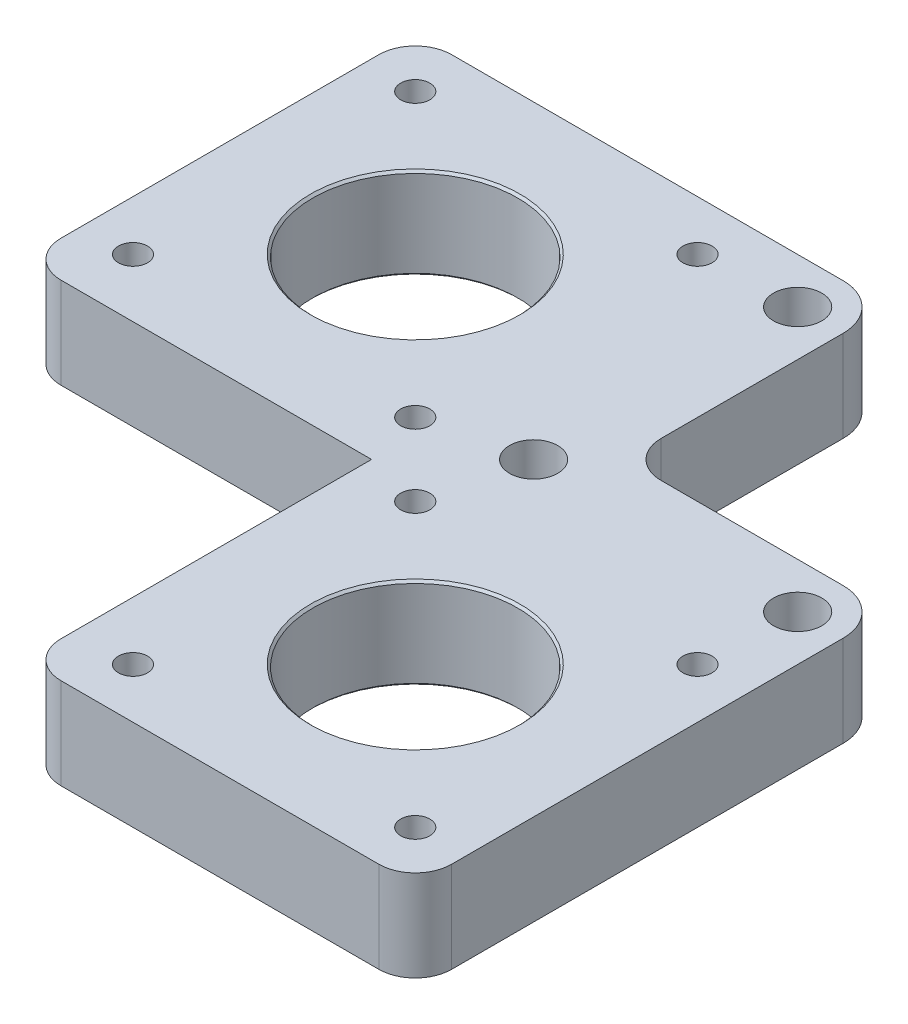
SolidWorks part; units mm, degrees
material "AISI 1045 Steel, cold drawn"
ref_plane "Front Plane" through (0, 0, 0) normal (0, 0, 1) x (1, 0, 0)
ref_plane "Top Plane" through (0, 0, 0) normal (0, 1, 0) x (1, 0, 0)
ref_plane "Right Plane" through (0, 0, 0) normal (1, 0, 0) x (0, 0, -1)
sketch "Sketch1" plane through (0, 0, 0) normal (0, 1, 0) x (1, 0, 0)
  line L1 (60, -21) -> (18, -21) construction
  line L2 (60, -21) -> (60, 21) construction
  line L3 (60, 21) -> (18, 21) construction
  line L4 (18, -21) -> (18, 21) construction
  line L5 (60, -21) -> (18, 21) construction
  line L6 (60, 21) -> (18, -21) construction
  line L7 (21, 18) -> (-21, 18) construction
  line L8 (21, 18) -> (21, 60) construction
  line L9 (21, 60) -> (-21, 60) construction
  line L10 (-21, 18) -> (-21, 60) construction
  line L11 (21, 18) -> (-21, 60) construction
  line L12 (21, 60) -> (-21, 18) construction
  line L14 (60, -21) -> (60, 31)
  line L15 (60, 31) -> (31, 31)
  line L16 (31, 31) -> (31, 60)
  line L17 (31, 60) -> (-21, 60)
  line L18 (-21, 60) -> (-21, 18)
  line L19 (-21, 18) -> (18, 18)
  line L20 (18, 18) -> (18, -21)
  line L21 (18, -21) -> (60, -21)
  point P0 (39, 0)
  point P5 (0, 39)
  dimension "D1" = 42
  dimension "D2" = 39
  dimension "D3" = 39
  dimension "D4" = 10
  dimension "D5" = 10
extrude "Boss-Extrude1" add sketch "Sketch1" along normal blind 10
hole_wizard "Ø22.5 (22.5) Diameter Hole1" positions "Sketch5" profile "Sketch7" hole size "Ø22.5" standard "ANSI Metric" end condition through all
sketch "Sketch5" plane through (0, 10, 0) normal (0, 1, 0) x (1, 0, 0)
  point P0 (0, 39)
  point P3 (39, 0)
sketch "Sketch7" plane through (0, 10, -39) normal (1, 0, 0) x (0, 0, 1)
  line L0 (0, 0) -> (0, 10)
  line L1 (0, 10) -> (11.25, 10)
  line L2 (11.25, 10) -> (11.25, 0)
  line L5 (11.25, 0) -> (0, 0)
  line L11 (0, -6.35) -> (0, 107.95) construction
  dimension "Thru Hole Dia." = 22.5
  dimension "Thru Hole Depth" = 10
sketch "Sketch8" plane through (0, 0, 0) normal (0, 1, 0) x (1, 0, 0)
  line L0 (21, 60) -> (-21, 18) construction
  line L1 (15.5, 23.5) -> (-15.5, 23.5)
  line L2 (15.5, 23.5) -> (15.5, 54.5)
  line L3 (15.5, 54.5) -> (-15.5, 54.5)
  line L4 (-15.5, 23.5) -> (-15.5, 54.5)
  line L5 (15.5, 23.5) -> (-15.5, 54.5) construction
  line L6 (15.5, 54.5) -> (-15.5, 23.5) construction
  line L7 (21, 18) -> (-21, 60) construction
  line L8 (60, 21) -> (18, -21) construction
  line L9 (23.5, -15.5) -> (54.5, -15.5)
  line L10 (23.5, -15.5) -> (23.5, 15.5)
  line L11 (23.5, 15.5) -> (54.5, 15.5)
  line L12 (54.5, -15.5) -> (54.5, 15.5)
  line L13 (23.5, -15.5) -> (54.5, 15.5) construction
  line L14 (23.5, 15.5) -> (54.5, -15.5) construction
  point P0 (0, 39)
  point P9 (39, 0)
  point P17 (39.0542, 0)
  point P19 (0, 0)
  dimension "D1" = 31
hole_wizard "CBORE for M3 SHCS1" positions "Sketch9" profile "Sketch10" counterbore size "M3" standard "ANSI Metric" end condition through all
sketch "Sketch9" plane through (0, 0, 0) normal (0, -1, 0) x (-1, 0, 0)
  point P0 (-54.5, 15.5)
  point P3 (-23.5, 15.5)
  point P6 (-23.5, -15.5)
  point P9 (-54.5, -15.5)
  point P12 (-15.5, 54.5)
  point P15 (-15.5, 23.5)
  point P18 (15.5, 23.5)
  point P21 (15.5, 54.5)
sketch "Sketch10" plane through (54.5, 0, -15.5) normal (1, 0, 0) x (0, 0, -1)
  line L0 (0, 0) -> (0, 10)
  line L1 (0, 10) -> (1.6, 10)
  line L3 (1.6, 10) -> (1.6, 3)
  line L4 (1.6, 3) -> (3.25, 3)
  line L5 (3.25, 3) -> (3.25, 0)
  line L7 (3.25, 0) -> (0, 0)
  line L11 (0, -6.35) -> (0, 107.95) construction
  dimension "Thru Hole Dia." = 3.2
  dimension "Thru Hole Depth" = 10
  dimension "C'Bore Dia." = 6.5
  dimension "C'Bore Depth" = 3
hole_wizard "M5 Clearance Hole1" positions "Sketch11" profile "Sketch12" hole size "M5" standard "ANSI Metric" end condition through all
sketch "Sketch11" plane through (0, 10, 0) normal (0, 1, 0) x (1, 0, 0)
  line L0 (55, 26) -> (26, 26) construction
  line L1 (26, 26) -> (26, 55) construction
  line L3 (31, 31) -> (31, 60) construction
  line L4 (31, 60) -> (-21, 60) construction
  line L5 (60, -21) -> (60, 31) construction
  line L6 (60, 31) -> (31, 31) construction
  point P0 (26, 55)
  point P2 (26, 26)
  point P4 (55, 26)
  dimension "D1" = 5
  dimension "D2" = 5
  dimension "D3" = 5
  dimension "D4" = 5
sketch "Sketch12" plane through (26, 10, -55) normal (1, 0, 0) x (0, 0, 1)
  line L0 (0, 0) -> (0, 10)
  line L1 (0, 10) -> (2.65, 10)
  line L2 (2.65, 10) -> (2.65, 0)
  line L5 (2.65, 0) -> (0, 0)
  line L11 (0, -6.35) -> (0, 107.95) construction
  dimension "Thru Hole Dia." = 5.3
  dimension "Thru Hole Depth" = 10
hole_wizard "Tap Drill for M5x0.8 Tap1" positions "Sketch13" profile "Sketch15" hole size "M5x0.8" standard "ANSI Metric"
sketch "Sketch13" plane through (0, 0, -18) normal (0, 0, 1) x (1, 0, 0)
  line L3 (-21, 10) -> (-21, 0) construction
  point P0 (5, 5)
  point P2 (-8.75, 5)
  point P22 (-21, 5)
  dimension "D1" = 8.75
  dimension "D2" = 5
sketch "Sketch15" plane through (5, 5, -18) normal (1, 0, 0) x (0, -1, 0)
  line L0 (0, 0) -> (0, 9.2618)
  line L1 (0, 9.2618) -> (2.1, 8)
  line L2 (2.1, 8) -> (2.1, 0)
  line L5 (2.1, 0) -> (0, 0)
  line L10 (0, 9.2618) -> (-2.1, 8) construction
  line L11 (0, -6.35) -> (0, 107.95) construction
  dimension "Hole Dia." = 4.2
  dimension "Hole Depth" = 8
  dimension "Drill Angle" = 118
ref_plane "Plane1" through (0, 0, 0) normal (0.7071, 0, 0.7071) x (0.7071, 0, -0.7071)
mirror "Mirror1" about plane through (0, 0, 0) normal (0.7071, 0, 0.7071) of "Tap Drill for M5x0.8 Tap1"
sketch "Sketch16" plane through (0, 10, 0) normal (0, 1, 0) x (1, 0, 0)
  line L1 (17.1, 17.1) -> (-21, 17.1)
  line L2 (17.1, 17.1) -> (17.1, -21)
  line L6 (-21, 17.1) -> (-21, 18)
  line L7 (-21, 18) -> (18, 18)
  line L8 (18, 18) -> (18, -21)
  line L9 (18, -21) -> (17.1, -21)
  circle A0 centre (39, 0) radius 11.25 construction
  dimension "D1" = 21.9
extrude "Boss-Extrude2" add sketch "Sketch16" against normal up to surface (10 mm away) up to face at (26, 0, -52.35)
fillet "Fillet2" radius 4 5 edges at (-21, 5, -60) (31, 5, -31) (60, 5, 21) (17.1, 5, 21) (-21, 5, -17.1)
fillet "Fillet3" radius 5 2 edges at (60, 5, -31) (31, 5, -60)
chamfer "Chamfer1" distance 0.25 angle 45 4 edges at (39, 10, 11.25) (39, 0, 11.25) (0, 10, -27.75) (0, 0, -27.75)
